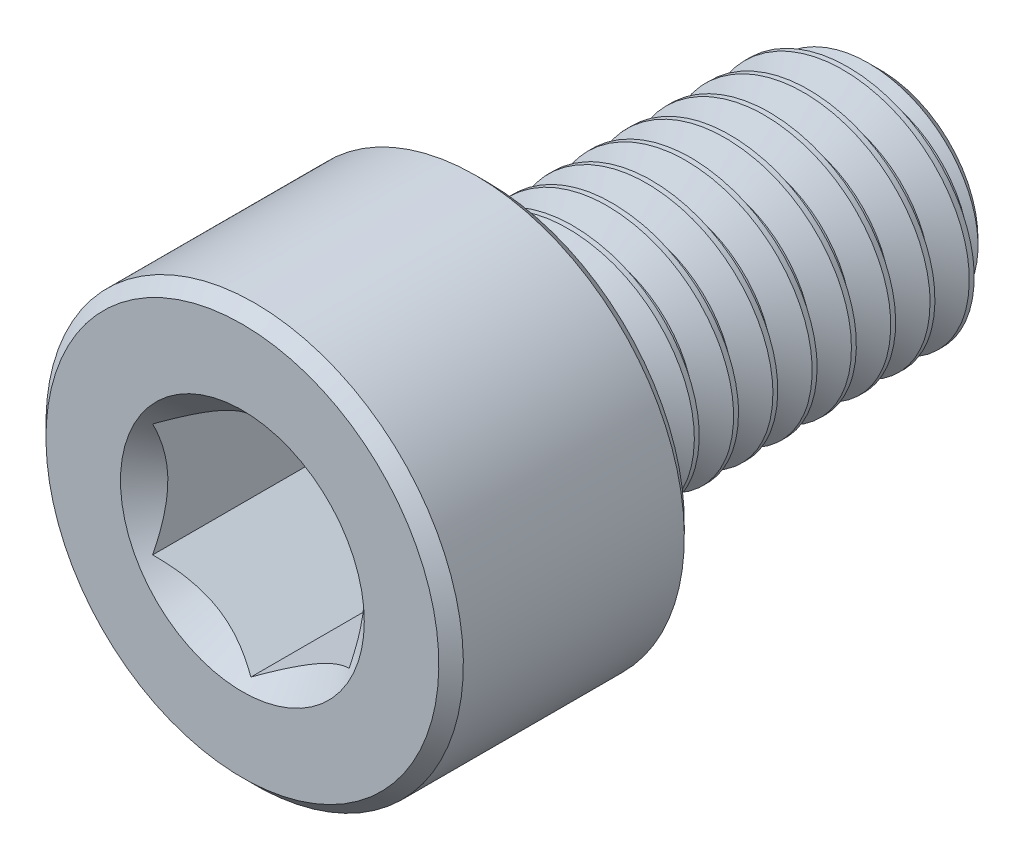
SolidWorks part; units mm, degrees
ref_plane "Front Plane" through (0, 0, 0) normal (0, 0, 1) x (1, 0, 0)
ref_plane "Top Plane" through (0, 0, 0) normal (0, 1, 0) x (1, 0, 0)
ref_plane "Right Plane" through (0, 0, 0) normal (1, 0, 0) x (0, 0, -1)
sketch "Sketch1" plane through (0, 0, 0) normal (1, 0, 0) x (0, 0, -1)
  line L0 (-6.5, 0) -> (6.5, 0) construction
  line L1 (6.5, 0) -> (6.5, 1.9804) construction
  line L2 (6.5, 1.9804) -> (5.9804, 2.5) construction
  line L3 (5.9804, 2.5) -> (5.9, 2.5) construction
  line L4 (5.9, 2.5) -> (-1.5, 2.5) construction
  line L5 (-1.5, 2.5) -> (-1.5, 4.25) construction
  line L6 (-1.5, 4.25) -> (-6.5, 4.25) construction
  line L7 (-6.5, 4.25) -> (-6.5, 0) construction
  line L8 (6.5, 1.9804) -> (6.5, 2.5) construction
  line L9 (6.45, 2.5866) -> (6.85, 1.8938) construction
  line L10 (6.85, 1.8938) -> (7.25, 2.5866) construction
  line L11 (7.25, 2.5866) -> (6.45, 2.5866) construction
  line L12 (6.85, 2.5866) -> (6.85, 2.5) construction
  line L13 (6.85, 1.8938) -> (6.85, 1.9804) construction
  line L14 (6.8, 1.9804) -> (6.9, 1.9804) construction
  line L15 (6.5, 2.5) -> (7.2, 2.5) construction
  line L16 (6.475, 2.5433) -> (7.225, 2.5433) construction
  line L17 (6.5, 0) -> (6.5, -2.5) construction
  line L18 (-1.75, 4.25) -> (-1.5, 4) construction
  line L19 (-6.25, 4.25) -> (-6.5, 4) construction
  line L20 (-1.5, 2.5) -> (-1.5, 0) construction
  line L21 (-1.5, 1.25) -> (1.1667, 1.25) construction
  line L22 (1.1667, 1.25) -> (3.8333, 1.25) construction
  line L23 (3.8333, 1.25) -> (6.5, 1.25) construction
  line L24 (1.1667, 1.25) -> (1.1667, 2.5) construction
  line L25 (1.1667, 2.5) -> (1.1667, 4.25) construction
  line L26 (3.8333, 1.25) -> (3.8333, 4.25) construction
  point P0 (-6.5, 2)
  point P3 (4.5, 2.5)
  point P4 (0, 0)
  point P18 (3.8333, 2.5)
  point P22 (6.85, 1.9804)
  point P24 (5.9, 2.5)
  point P25 (6.85, 2.5)
  point P28 (6.85, 2.5433)
  point P29 (4.5, -2.5)
  point P30 (1.1667, 2.5)
  point P31 (-4, 4.25)
  point P37 (-2.375, 4.25)
  point P38 (-6.125, 4.25)
  point P45 (1.1667, 1.25)
  point P46 (3.8333, 1.25)
  dimension "D7" = 0.25
  dimension "D8" = 0.25
  dimension "D9" = 0.25
  dimension "D10" = 0.125
  dimension "D11" = 0.625
  dimension "Drive Size" = 4
  dimension "Head Diameter" = 8.5
  dimension "Head Height" = 5
  dimension "Thread Pitch" = 0.8
  dimension "Thread Dia" = 5
  dimension "Length" = 8
  dimension "D12" = 0.6
  dimension "D4" = 2
  dimension "D3" = 45
sketch "Sketch2" plane through (0, 0, 0) normal (1, 0, 0) x (0, 0, -1)
  line L0 (-6.5, 0) -> (-6.5, 4)
  line L1 (-6.25, 4.25) -> (-1.75, 4.25)
  line L2 (-1.5, 4) -> (-1.5, 2.75)
  line L4 (5.9804, 2.5) -> (6.5, 1.9804)
  line L5 (6.5, 1.9804) -> (6.5, 0)
  line L6 (-1.5, 4.25) -> (-6.5, 4.25) construction
  line L7 (6.5, 0) -> (-6.5, 0)
  line L8 (-6.25, 4.25) -> (-6.5, 4) construction
  line L10 (-6.25, 4.25) -> (-6.5, 4)
  line L14 (-1.75, 4.25) -> (-1.5, 4) construction
  line L16 (-1.75, 4.25) -> (-1.5, 4)
  line L17 (-1.5, 2.5) -> (-1.5, 4.25) construction
  line L19 (-1.25, 2.5) -> (5.9804, 2.5)
  line L20 (5.9, 2.5) -> (-1.5, 2.5) construction
  arc A1 (-1.5, 2.75) -> (-1.25, 2.5) centre (-1.25, 2.75) ccw
  dimension "D3" = 0.25
revolve "Revolve1" add sketch "Sketch2" angle 360 about L7
sketch "Sketch3" plane through (0, 0, 6.5) normal (0, 0, 1) x (1, 0, 0)
  line L1 (2, -1.1547) -> (2, 1.1547)
  line L2 (2, 1.1547) -> (0, 2.3094)
  line L3 (0, 2.3094) -> (-2, 1.1547)
  line L4 (-2, 1.1547) -> (-2, -1.1547)
  line L5 (-2, -1.1547) -> (0, -2.3094)
  line L6 (0, -2.3094) -> (2, -1.1547)
  circle A0 centre (0, 0) radius 2 construction
  circle A1 centre (0, 0) radius 4.25 construction
  circle A2 centre (0, 0) radius 4.25 construction
  circle A3 centre (0, 0) radius 2.3094 construction
  point P13 (0, 0)
  dimension "D1" = 4.6188
extrude "Cut-Extrude1" cut sketch "Sketch3" against normal offset from surface (4 mm away) 1 up to face at (0, 4, 1.5)
sketch "Sketch4" plane through (0, 0, 6.5) normal (0, 0, 1) x (1, 0, 0)
  circle A0 centre (0, 0) radius 2.4826
  dimension "D1" = 4.9652
extrude "Cut-Extrude2" cut sketch "Sketch4" against normal up to vertex (2.5 mm away) draft 45 up to point (0, 4.25, 4)
sketch "Sketch11" plane through (0, 0, 0) normal (1, 0, 0) x (0, 0, -1)
  line L0 (-6.5, 0) -> (6.5, 0) construction
  line L1 (-6.5, 0) -> (6.5, 0) construction
  line L2 (0, 0) -> (0, 2.5) construction
  line L3 (5.9, 2.5) -> (-1.5, 2.5) construction
  line L4 (5, 0) -> (5, 2.5) construction
  line L6 (6.5, 1.9804) -> (6.5, 2.5) construction
  point P2 (0, 0)
  point P3 (5, 0)
  dimension "D1" = 1.5
  dimension "D2" = 1.5
sketch "Sketch6" plane through (0, 0, -6.5) normal (0, 0, -1) x (-1, 0, 0)
  circle A0 centre (0, 0) radius 2.5
curve "Helix/Spiral1" pitch 0.8 height 8.8 turns 11
sketch "Sketch10" plane through (0, 0, 0) normal (1, 0, 0) x (0, 0, -1)
  line L0 (-1.25, -4.25) -> (-1.25, 4.25)
  line L5 (-6.5, 0) -> (6.5, 0) construction
  line L6 (-1.25, 2.5) -> (-1.25, -2.5) construction
  point P3 (-1.25, 0)
split "Split1" trim tools "Sketch10" bodies to split 106 resulting bodies 114 115
sketch "Sketch7" plane through (0, 0, 0) normal (1, 0, 0) x (0, 0, -1)
  line L0 (6.475, 2.5433) -> (7.225, 2.5433)
  line L1 (7.225, 2.5433) -> (6.9, 1.9804)
  line L2 (6.9, 1.9804) -> (6.8, 1.9804)
  line L3 (6.8, 1.9804) -> (6.475, 2.5433)
sweep "Cut-Sweep1" cut profiles "Sketch7" path "Helix/Spiral1" align with end faces yes
sketch "Sketch8" plane through (0, 0, 0) normal (1, 0, 0) x (0, 0, -1)
  line L0 (-1.5, 0) -> (-1.5, 2.5)
  line L1 (-1.25, -2.5) -> (-1.25, 2.5) construction
  line L2 (-1.5, 2.5) -> (-1.25, 2.5)
  line L4 (-1.25, 2.5) -> (0.1934, 0)
  line L5 (0.1934, 0) -> (-1.5, 0)
  line L6 (5.9, 2.5) -> (-1.5, 2.5) construction
  line L7 (-6.5, 0) -> (6.5, 0) construction
  dimension "D1" = 60
revolve "Revolve2" add sketch "Sketch8" angle 360 about L5
equation "\"D2@Sketch1\" = \"Thread Pitch@Sketch1\" / 8"
equation "\"D4@Helix/Spiral1\" = \"Thread Pitch@Sketch1\""
equation "\"D7@Sketch1\" = \"Head Height@Sketch1\" * .05"
equation "\"D8@Sketch1\"=\"D7@Sketch1\""
equation "\"D9@Sketch1\"=\"D7@Sketch1\""
equation "\"D10@Sketch1\"=\"D7@Sketch1\"/2"
equation "\"D11@Sketch1\"=\"D10@Sketch1\"*5"
equation "\"D4@Sketch1\"=\"Thread Pitch@Sketch1\"*2.5"
equation "\"D12@Sketch1\"=\"Thread Pitch@Sketch1\"*.75"
equation "\"D3@Helix/Spiral1\"=\"Length@Sketch1\"+\"Thread Pitch@Sketch1\""
equation "\"D3@Sketch2\"=\"Thread Dia@Sketch1\"*0.05"
equation "\"D1@Sketch11\"=\"Length@Sketch1\"*0.1875"
equation "\"D2@Sketch11\"=\"D1@Sketch11\""
equation "\"D1@Sketch4\"=\"D1@Sketch3\"*1.075"
